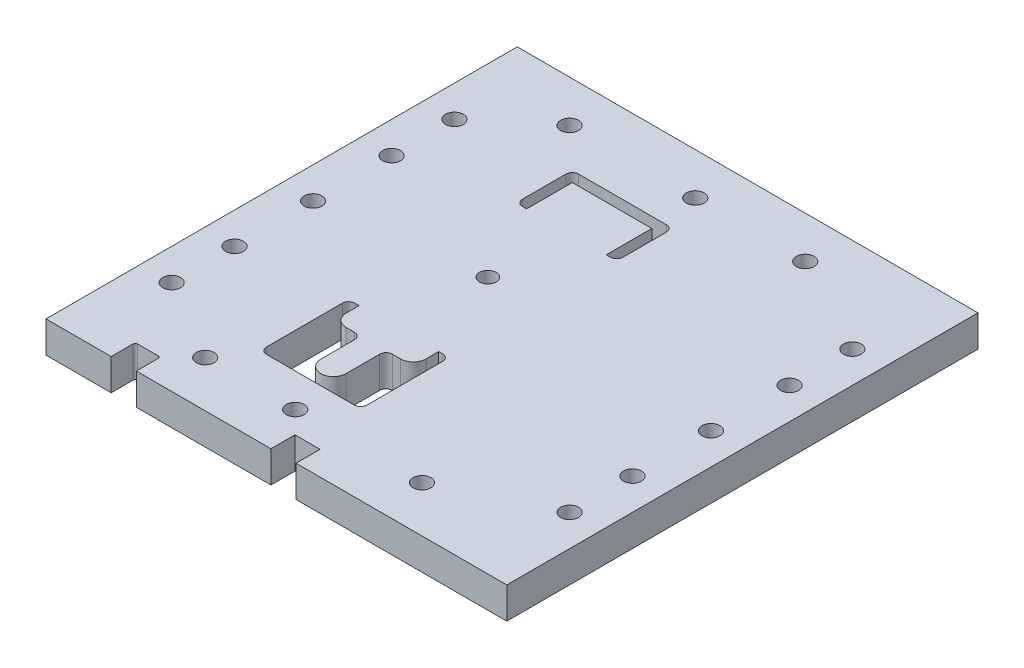
SolidWorks part; units mm, degrees
material "Plain Carbon Steel"
ref_plane "Front Plane" through (0, 0, 0) normal (0, 0, 1) x (1, 0, 0)
ref_plane "Top Plane" through (0, 0, 0) normal (0, 1, 0) x (1, 0, 0)
ref_plane "Right Plane" through (0, 0, 0) normal (1, 0, 0) x (0, 0, -1)
sketch "Sketch1" plane through (0, 0, 0) normal (0, 1, 0) x (1, 0, 0)
  line L1 (-110, -112.5) -> (110, -112.5)
  line L2 (-110, -112.5) -> (-110, 112.5)
  line L3 (-110, 112.5) -> (110, 112.5)
  line L4 (110, -112.5) -> (110, 112.5)
  line L5 (-110, -112.5) -> (110, 112.5) construction
  line L6 (-110, 112.5) -> (110, -112.5) construction
  point P0 (0, 0)
  dimension "D1" = 225
  dimension "D2" = 220
extrude "Boss-Extrude1" add sketch "Sketch1" against normal blind 15
sketch "Sketch2" plane through (0, 0, 0) normal (0, 1, 0) x (1, 0, 0)
  line L0 (-21.75, 69.53) -> (-21.75, -69.53) construction
  circle A0 centre (-21.75, 10.23) radius 4
  circle A4 centre (-21.75, 10.23) radius 5 construction
  dimension "D1" = 8
extrude "Cut-Extrude1" cut sketch "Sketch2" against normal up to next
sketch "Sketch3" plane through (0, -15, 0) normal (0, -1, 0) x (1, 0, 0)
  line L0 (-68.37, 102) -> (-77.37, 102) construction
  line L78 (-72.87, 102) -> (-72.87, 112.5) construction
  line L79 (-110, 112.5) -> (110, 112.5) construction
  line L80 (3.38, 102) -> (3.38, 112.5) construction
  line L81 (7.88, 102) -> (-1.12, 102) construction
  line L82 (-1.62, 102.5) -> (-1.62, 115) construction
  line L83 (-77.87, 101) -> (-67.87, 101)
  line L84 (-78.87, 102) -> (-78.87, 112.5)
  line L85 (-78.87, 112.5) -> (-66.87, 112.5)
  line L86 (-66.87, 102) -> (-66.87, 112.5)
  line L87 (-2.62, 101) -> (9.38, 101)
  line L88 (-2.62, 101) -> (-2.62, 112.5)
  line L89 (-2.62, 112.5) -> (9.38, 112.5)
  line L90 (9.38, 101) -> (9.38, 112.5)
  line L91 (8.38, 115) -> (8.38, 102.5) construction
  line L92 (-67.87, 115) -> (-67.87, 102.5) construction
  line L93 (-77.87, 102.5) -> (-77.87, 115) construction
  arc A0 (-67.87, 101) -> (-66.87, 102) centre (-67.87, 102) ccw
  arc A1 (-77.87, 101) -> (-78.87, 102) centre (-77.87, 102) cw
  dimension "D7" = 1
  dimension "D1" = 1
  dimension "D2" = 1
  dimension "D3" = 1
  dimension "D4" = 1
  dimension "D5" = 1
  dimension "D6" = 1
extrude "Cut-Extrude2" cut sketch "Sketch3" against normal up to next
sketch "Sketch4" plane through (0, -15, 0) normal (0, -1, 0) x (1, 0, 0)
  circle A0 centre (-35, 100) radius 8.5
  circle A1 centre (25, 100) radius 8.5
  circle A2 centre (70, 100) radius 8.5
  circle A3 centre (-35, -100) radius 8.5
  circle A4 centre (25, -100) radius 8.5
  circle A5 centre (70, -100) radius 8.5
  dimension "D1" = 17
extrude "Cut-Extrude3" cut sketch "Sketch4" against normal blind 5
hole_wizard "M10 Tapped Hole2" positions "Sketch27" profile "Sketch9" tap size "M10" standard "ISO" end condition through all
sketch "Sketch27" plane through (0, 0, 0) normal (0, 1, 0) x (1, 0, 0)
  line L1 (110, 112.5) -> (-110, 112.5) construction
  line L2 (-110, 112.5) -> (-110, -112.5) construction
  line L3 (0, 112.5) -> (0, -112.5) construction
  line L5 (-66.87, -112.5) -> (-2.62, -112.5) construction
  line L6 (-110, -112.5) -> (-78.87, -112.5) construction
  circle A0 centre (-95, 67.5) radius 12.5 construction
  circle A1 centre (-95, 37.5) radius 12.5 construction
  circle A2 centre (-95, -67.5) radius 12.5 construction
  circle A3 centre (95, -37.5) radius 12.5 construction
  point P0 (-95, -67.5)
  point P2 (-95, -37.5)
  point P4 (-95, 0)
  point P6 (-95, 37.5)
  point P8 (-95, 67.5)
  point P28 (95, 67.5)
  point P29 (95, 37.5)
  point P30 (95, 0)
  point P31 (95, -37.5)
  point P32 (95, -67.5)
  dimension "D1" = 25
  dimension "D2" = 45
  dimension "D3" = 30
  dimension "D4" = 37.5
  dimension "D5" = 37.5
  dimension "D6" = 45
  dimension "D7" = 15
sketch "Sketch9" plane through (-95, 0, 67.5) normal (1, 0, 0) x (0, 0, 1)
  line L0 (0, 0) -> (0, 15)
  line L1 (0, 15) -> (4.25, 15)
  line L2 (4.25, 15) -> (4.25, 0)
  line L5 (4.25, 0) -> (0, 0)
  line L11 (0, -6.35) -> (0, 107.95) construction
  dimension "Thru Tap Drill Dia." = 8.5
  dimension "Thru Tap Drill Depth" = 15
cosmetic thread "Hole Thread23" parameters "D2"=10
cosmetic thread "Hole Thread24" parameters "D2"=10
cosmetic thread "Hole Thread25" parameters "D2"=10
cosmetic thread "Hole Thread26" parameters "D2"=10
cosmetic thread "Hole Thread27" parameters "D2"=10
cosmetic thread "Hole Thread28" parameters "D2"=10
cosmetic thread "Hole Thread29" parameters "D2"=10
cosmetic thread "Hole Thread30" parameters "D2"=10
cosmetic thread "Hole Thread31" parameters "D2"=10
cosmetic thread "Hole Thread32" parameters "D2"=10
hole_wizard "M10 Tapped Hole3" positions "Sketch18" profile "Sketch15" tap size "M10" standard "ISO" end condition through all
sketch "Sketch18" plane through (0, 0, 0) normal (0, 1, 0) x (1, 0, 0)
  line L0 (-110, 112.5) -> (-110, -112.5) construction
  line L1 (110, 112.5) -> (-110, 112.5) construction
  circle A0 centre (-65, 92.5) radius 12.5 construction
  circle A1 centre (-95, 67.5) radius 12.5 construction
  circle A2 centre (95, 67.5) radius 12.5 construction
  circle A4 centre (47.5, 92.5) radius 12.5 construction
  circle A5 centre (-5, 92.5) radius 12.5 construction
  point P0 (-65, 92.5)
  point P2 (-5, 92.5)
  point P4 (47.5, 92.5)
  dimension "D1" = 25
  dimension "D2" = 45
  dimension "D3" = 60
  dimension "D4" = 52.5
  dimension "D6" = 20
sketch "Sketch15" plane through (-65, 0, -92.5) normal (1, 0, 0) x (0, 0, 1)
  line L0 (0, 0) -> (0, 15)
  line L1 (0, 15) -> (4.25, 15)
  line L2 (4.25, 15) -> (4.25, 0)
  line L5 (4.25, 0) -> (0, 0)
  line L11 (0, -6.35) -> (0, 107.95) construction
  dimension "Thru Tap Drill Dia." = 8.5
  dimension "Thru Tap Drill Depth" = 15
cosmetic thread "Hole Thread34" parameters "D2"=10
cosmetic thread "Hole Thread35" parameters "D2"=10
cosmetic thread "Hole Thread36" parameters "D2"=10
sketch "Sketch20" plane through (0, 0, 0) normal (0, 1, 0) x (1, 0, 0)
  line L5 (110, 112.5) -> (-110, 112.5) construction
  line L6 (110, -112.5) -> (110, 112.5) construction
  line L7 (-110, 112.5) -> (-110, -112.5) construction
  line L8 (9.38, -112.5) -> (110, -112.5) construction
  circle A2 centre (-13, -90.5) radius 12.5 construction
  circle A5 centre (55, -15.5) radius 12.5 construction
  circle A6 centre (47.5, -90.5) radius 12.5 construction
  circle A7 centre (-53, 32.5) radius 12.5 construction
  circle A8 centre (-53, -17.5) radius 12.5 construction
  circle A10 centre (55, 61) radius 12.5 construction
  circle A12 centre (3, 10.5) radius 12.5 construction
  circle A14 centre (-65, 92.5) radius 12.5 construction
  circle A15 centre (-5, 92.5) radius 12.5 construction
  circle A16 centre (47.5, 92.5) radius 12.5 construction
  circle A17 centre (-56, -90.5) radius 12.5 construction
  point P26 (0, 0)
  dimension "D8" = 25
  dimension "D13" = 80
  dimension "D2" = 55
  dimension "D3" = 57
  dimension "D4" = 102
  dimension "D5" = 113
  dimension "D6" = 128
  dimension "D7" = 22
  dimension "D9" = 97
  dimension "D10" = 62.5
  dimension "D11" = 50
  dimension "D12" = 51.5
  dimension "D14" = 54
hole_wizard "M10 Tapped Hole4" positions "Sketch30" profile "Sketch22" tap size "M10" standard "ISO" end condition through all
sketch "Sketch30" plane through (0, 0, 0) normal (0, 1, 0) x (1, 0, 0)
  point P15 (-13, -90.5)
  point P18 (47.5, -90.5)
  point P22 (-56, -90.5)
  point P27 (0, 0)
  point P28 (0, 0)
  point P29 (0, 0)
  point P30 (0, 0)
  point P31 (0, 0)
sketch "Sketch22" plane through (-13, 0, 90.5) normal (1, 0, 0) x (0, 0, 1)
  line L0 (0, 0) -> (0, 15)
  line L1 (0, 15) -> (4.25, 15)
  line L2 (4.25, 15) -> (4.25, 0)
  line L5 (4.25, 0) -> (0, 0)
  line L11 (0, -6.35) -> (0, 107.95) construction
  dimension "Thru Tap Drill Dia." = 8.5
  dimension "Thru Tap Drill Depth" = 15
cosmetic thread "Hole Thread41" parameters "D2"=10
cosmetic thread "Hole Thread49" parameters "D2"=10
cosmetic thread "Hole Thread50" parameters "D2"=10
sketch "Sketch24" plane through (0, 0, 0) normal (0, 1, 0) x (1, 0, 0)
  line L22 (2.25, -35.27) -> (2.25, -71.53) construction
  line L27 (-45.75, -71.53) -> (-45.75, -35.27) construction
  line L28 (2.25, -35.27) -> (2.25, -71.53)
  line L29 (-45.75, -71.53) -> (-45.75, -35.27)
  line L30 (-42.75, -32.27) -> (-40.75, -32.27)
  line L31 (-2.75, -32.27) -> (-0.75, -32.27)
  line L32 (-42.75, -74.53) -> (-0.75, -74.53)
  line L37 (15.25, -32.27) -> (-2.75, -32.27)
  line L38 (-2.75, -32.27) -> (-2.75, -38.4)
  line L39 (-8.75, -44.4) -> (-12.75, -44.4)
  line L40 (-15.75, -47.4) -> (-15.75, -63.53)
  line L41 (-27.75, -63.53) -> (-27.75, -47.4)
  line L42 (-30.75, -44.4) -> (-34.75, -44.4)
  line L43 (-40.75, -38.4) -> (-40.75, -32.27)
  line L44 (-40.75, -32.27) -> (-58.75, -32.27)
  line L45 (-61.75, -35.27) -> (-61.75, -71.53)
  line L46 (-58.75, -74.53) -> (15.25, -74.53)
  line L47 (18.25, -71.53) -> (18.25, -35.27)
  line L49 (-2.75, -32.27) -> (-2.75, -38.4)
  line L50 (-8.75, -44.4) -> (-12.75, -44.4)
  line L51 (-15.75, -47.4) -> (-15.75, -63.53)
  line L52 (-27.75, -63.53) -> (-27.75, -47.4)
  line L53 (-30.75, -44.4) -> (-34.75, -44.4)
  line L54 (-40.75, -38.4) -> (-40.75, -32.27)
  arc A20 (2.25, -35.27) -> (-0.75, -32.27) centre (-0.75, -35.27) ccw construction
  arc A21 (-0.75, -74.53) -> (2.25, -71.53) centre (-0.75, -71.53) ccw construction
  arc A22 (-45.75, -71.53) -> (-42.75, -74.53) centre (-42.75, -71.53) ccw construction
  arc A23 (-42.75, -32.27) -> (-45.75, -35.27) centre (-42.75, -35.27) ccw construction
  arc A24 (2.25, -35.27) -> (-0.75, -32.27) centre (-0.75, -35.27) ccw
  arc A25 (-0.75, -74.53) -> (2.25, -71.53) centre (-0.75, -71.53) ccw
  arc A26 (-45.75, -71.53) -> (-42.75, -74.53) centre (-42.75, -71.53) ccw
  arc A27 (-42.75, -32.27) -> (-45.75, -35.27) centre (-42.75, -35.27) ccw
  arc A29 (-8.75, -44.4) -> (-2.75, -38.4) centre (-8.75, -38.4) ccw
  arc A30 (-12.75, -44.4) -> (-15.75, -47.4) centre (-12.75, -47.4) ccw
  arc A31 (-27.75, -63.53) -> (-15.75, -63.53) centre (-21.75, -63.53) ccw
  arc A32 (-27.75, -47.4) -> (-30.75, -44.4) centre (-30.75, -47.4) ccw
  arc A33 (-40.75, -38.4) -> (-34.75, -44.4) centre (-34.75, -38.4) ccw
  arc A34 (-58.75, -32.27) -> (-61.75, -35.27) centre (-58.75, -35.27) ccw
  arc A35 (-61.75, -71.53) -> (-58.75, -74.53) centre (-58.75, -71.53) ccw
  arc A36 (15.25, -74.53) -> (18.25, -71.53) centre (15.25, -71.53) ccw
  arc A37 (18.25, -35.27) -> (15.25, -32.27) centre (15.25, -35.27) ccw
  arc A38 (-8.75, -44.4) -> (-2.75, -38.4) centre (-8.75, -38.4) ccw
  arc A39 (-12.75, -44.4) -> (-15.75, -47.4) centre (-12.75, -47.4) ccw
  arc A40 (-27.75, -63.53) -> (-15.75, -63.53) centre (-21.75, -63.53) ccw
  arc A41 (-27.75, -47.4) -> (-30.75, -44.4) centre (-30.75, -47.4) ccw
  arc A42 (-40.75, -38.4) -> (-34.75, -44.4) centre (-34.75, -38.4) ccw
  dimension "D1" = 0
extrude "Cut-Extrude4" cut sketch "Sketch24" against normal up to next
sketch "Sketch29" plane through (0, -15, 0) normal (0, -1, 0) x (1, 0, 0)
  line L0 (-2.75, -47.73) -> (-0.75, -47.73) construction
  line L1 (-2.75, -16.73) -> (-2.75, -69.53) construction
  line L2 (2.25, -50.73) -> (2.25, -71.53) construction
  line L3 (-0.75, -74.53) -> (-42.75, -74.53) construction
  line L4 (-2.75, -69.53) -> (-40.75, -69.53) construction
  line L5 (-40.75, -69.53) -> (-40.75, -34.23) construction
  line L6 (-42.75, -47.73) -> (-40.75, -47.73) construction
  line L7 (-45.75, -71.53) -> (-45.75, -50.73) construction
  line L8 (-2.75, -47.73) -> (-0.75, -47.73)
  line L9 (-2.75, -47.73) -> (-2.75, -69.53)
  line L10 (2.25, -50.73) -> (2.25, -71.53)
  line L11 (-0.75, -74.53) -> (-42.75, -74.53)
  line L12 (-2.75, -69.53) -> (-40.75, -69.53)
  line L13 (-40.75, -69.53) -> (-40.75, -47.73)
  line L14 (-42.75, -47.73) -> (-40.75, -47.73)
  line L15 (-45.75, -71.53) -> (-45.75, -50.73)
  arc A0 (2.25, -50.73) -> (-0.75, -47.73) centre (-0.75, -50.73) ccw construction
  arc A1 (-0.75, -74.53) -> (2.25, -71.53) centre (-0.75, -71.53) ccw construction
  arc A2 (-45.75, -71.53) -> (-42.75, -74.53) centre (-42.75, -71.53) ccw construction
  arc A3 (-42.75, -47.73) -> (-45.75, -50.73) centre (-42.75, -50.73) ccw construction
  arc A4 (2.25, -50.73) -> (-0.75, -47.73) centre (-0.75, -50.73) ccw
  arc A5 (-0.75, -74.53) -> (2.25, -71.53) centre (-0.75, -71.53) ccw
  arc A6 (-45.75, -71.53) -> (-42.75, -74.53) centre (-42.75, -71.53) ccw
  arc A7 (-42.75, -47.73) -> (-45.75, -50.73) centre (-42.75, -50.73) ccw
extrude "Cut-Extrude6" cut sketch "Sketch29" against normal up to next
